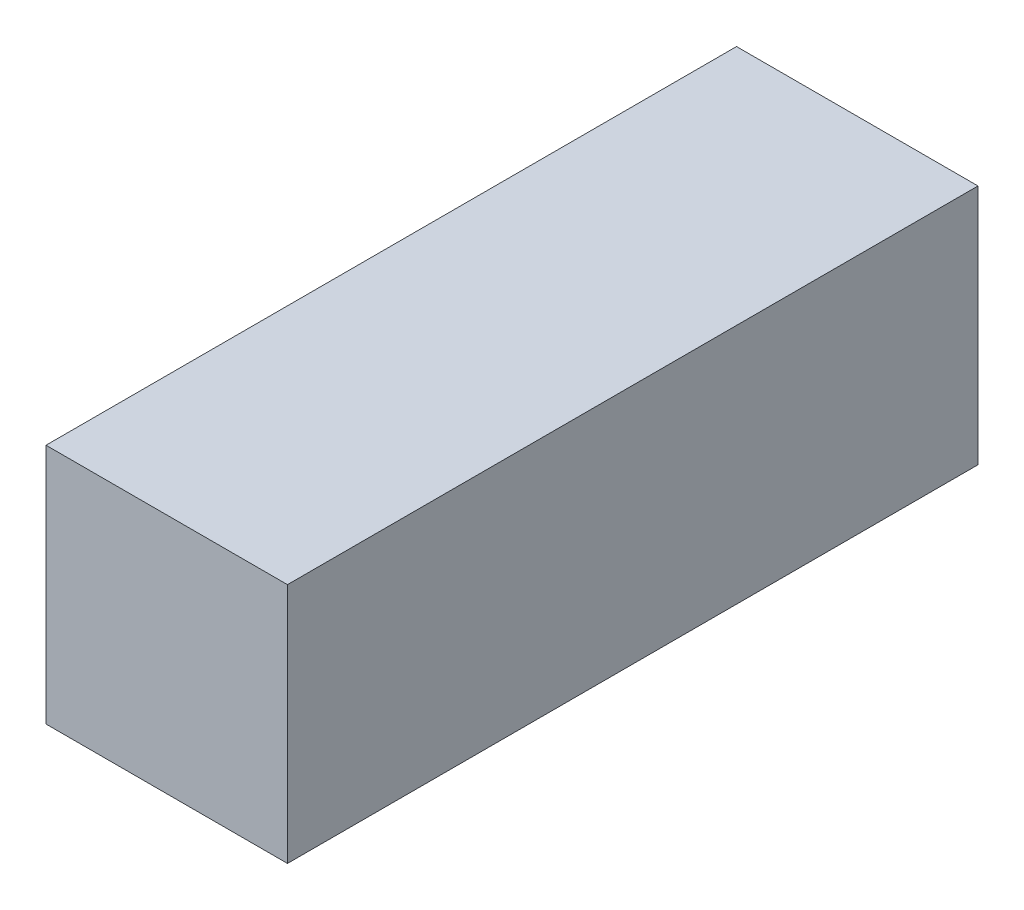
SolidWorks part; units mm, degrees
material "A-Glass Fiber"
ref_plane "Front Plane" through (0, 0, 0) normal (0, 0, 1) x (1, 0, 0)
ref_plane "Top Plane" through (0, 0, 0) normal (0, 1, 0) x (1, 0, 0)
ref_plane "Right Plane" through (0, 0, 0) normal (1, 0, 0) x (0, 0, -1)
sketch "Sketch1" plane through (0, 0, 0) normal (1, 0, 0) x (0, 0, -1)
  line L0 (-28.575, 0) -> (28.575, 0) construction
  line L1 (-28.575, 9.652) -> (28.575, 9.652)
  line L2 (-28.575, 9.652) -> (-28.575, -9.398)
  line L3 (-28.575, -9.398) -> (28.575, -9.398)
  line L4 (28.575, 9.652) -> (28.575, -9.398)
  dimension "D1" = 9.652
  dimension "D2" = 19.05
  dimension "D3" = 57.15
extrude "Boss-Extrude1" add sketch "Sketch1" along normal mid plane 19.05
sketch "Sketch2" plane through (0, 0, 0) normal (1, 0, 0) x (0, 0, -1)
  line L1 (-28.575, 9.652) -> (-28.575, -9.398) construction
  line L2 (-17.7349, -4.4901) -> (-12.827, -9.398)
  line L3 (-28.575, -9.398) -> (28.575, -9.398) construction
  line L4 (28.575, -9.398) -> (28.575, 9.652) construction
  line L5 (17.7349, -4.4901) -> (12.827, -9.398)
  line L6 (-19.795, 5.8666) -> (-18.227, 9.652)
  line L7 (12.827, -9.398) -> (-12.827, -9.398)
  line L8 (28.575, 9.652) -> (-28.575, 9.652) construction
  line L9 (-18.227, 9.652) -> (22.225, 9.652)
  line L10 (22.225, 9.652) -> (22.225, 6.35)
  line L11 (28.575, 9.652) -> (-28.575, 9.652) construction
  arc A0 (-19.795, 5.8666) -> (-17.7349, -4.4901) centre (-22.225, 0) ccw
  arc A1 (22.225, 6.35) -> (17.7349, -4.4901) centre (22.225, 0) cw
  dimension "D1" = 6.35
  dimension "D3" = 6.35
  dimension "D2" = 45
  dimension "D4" = 45
  dimension "D5" = 22.5
extrude "Cut-Extrude3" cut sketch "Sketch2" against normal through all both and the other way through all flip side to cut
sketch "Sketch7" plane through (0, 0, 0) normal (1, 0, 0) x (0, 0, -1)
  circle A0 centre (22.225, 0) radius 6.604
  arc A1 (17.7349, -4.4901) -> (22.225, 6.35) centre (22.225, 0) ccw construction
  dimension "D1" = 13.208
extrude "Cut-Extrude6" cut sketch "Sketch7" against normal mid plane 12.954
sketch "Sketch11" plane through (0, 0, 0) normal (1, 0, 0) x (0, 0, -1)
  circle A0 centre (-22.225, 0) radius 6.604
  arc A1 (-19.795, 5.8666) -> (-17.7349, -4.4901) centre (-22.225, 0) ccw construction
  dimension "D1" = 13.208
extrude "Cut-Extrude10" cut sketch "Sketch11" against normal mid plane 3.3528
sketch "Sketch8" plane through (9.525, 0, 0) normal (1, 0, 0) x (0, 0, -1)
  circle A0 centre (-22.225, 0) radius 6.604
  arc A1 (-19.795, 5.8666) -> (-17.7349, -4.4901) centre (-22.225, 0) ccw construction
  dimension "D1" = 13.208
extrude "Cut-Extrude7" cut sketch "Sketch8" against normal blind 3.556
sketch "Sketch9" plane through (-9.525, 0, 0) normal (-1, 0, 0) x (0, 0, 1)
  circle A0 centre (22.225, 0) radius 6.604
  arc A1 (17.7349, -4.4901) -> (19.795, 5.8666) centre (22.225, 0) ccw construction
  dimension "D1" = 13.208
extrude "Cut-Extrude8" cut sketch "Sketch9" against normal blind 3.556
sketch "Sketch10" plane through (0, 0, 0) normal (1, 0, 0) x (0, 0, -1)
  circle A0 centre (-22.225, 0) radius 1.5875
  circle A1 centre (22.225, 0) radius 3.175
  arc A2 (-19.795, 5.8666) -> (-17.7349, -4.4901) centre (-22.225, 0) ccw construction
  arc A3 (17.7349, -4.4901) -> (22.225, 6.35) centre (22.225, 0) ccw construction
  dimension "D1" = 3.175
  dimension "D2" = 6.35
extrude "Cut-Extrude9" cut sketch "Sketch10" against normal through all both and the other way through all
sketch "Sketch12" plane through (0, 0, 0) normal (0, 0, 1) x (1, 0, 0)
  line L0 (-9.525, 9.652) -> (9.525, 9.652) construction
  line L1 (-1.6764, 9.652) -> (1.6764, 9.652)
  line L2 (-1.6764, 9.652) -> (-1.6764, 3.175)
  line L3 (-1.6764, 3.175) -> (1.6764, 3.175)
  line L4 (1.6764, 9.652) -> (1.6764, 3.175)
  line L5 (0, -9.398) -> (0, 9.652) construction
  line L6 (-9.525, -9.398) -> (9.525, -9.398) construction
  line L7 (-1.6764, -4.6697) -> (-1.6764, 6.1013) construction
  dimension "D1" = 3.175
extrude "Cut-Extrude11" cut sketch "Sketch12" against normal through all both and the other way through all
sketch "Sketch13" plane through (0, 0, 0) normal (1, 0, 0) x (0, 0, -1)
  line L1 (-12.573, 6.4389) -> (12.4118, 6.4389)
  line L2 (-12.573, 6.4389) -> (-12.573, 3.0861)
  line L3 (-12.573, 3.0861) -> (12.4118, 3.0861)
  line L4 (12.4118, 6.4389) -> (12.4118, 3.0861)
  line L5 (-12.573, 4.7625) -> (12.4118, 4.7625) construction
  circle A0 centre (-22.225, 0) radius 1.5875 construction
  circle A2 centre (-14.0128, 4.7625) radius 0.7937
  circle A3 centre (22.225, 0) radius 3.175 construction
  dimension "D5" = 1.5875
  dimension "D6" = 7.112
  dimension "D4" = 7.112
  dimension "D1" = 3.3528
  dimension "D2" = 4.7625
  dimension "D3" = 9.652
extrude "Cut-Extrude12" cut sketch "Sketch13" against normal through all both and the other way through all
sketch "Sketch14" plane through (0, 0, 0) normal (1, 0, 0) x (0, 0, -1)
  line L0 (-15.875, -6.35) -> (-12.827, -9.398)
  line L1 (-17.5553, -4.6697) -> (-12.827, -9.398) construction
  line L2 (-12.827, -9.398) -> (12.827, -9.398)
  line L3 (12.827, -9.398) -> (15.875, -6.35)
  line L4 (15.875, -6.35) -> (-15.875, -6.35)
  line L7 (12.827, -9.398) -> (17.7349, -4.4901) construction
  line L8 (-14.351, -7.874) -> (14.351, -7.874) construction
  circle A0 centre (-22.225, 0) radius 1.5875 construction
  dimension "D1" = 6.35
extrude "Cut-Extrude13" cut sketch "Sketch14" against normal mid plane 3.175
sketch "Sketch16" plane through (0, 0, 0) normal (1, 0, 0) x (0, 0, -1)
  circle A0 centre (-12.827, -7.9375) radius 0.7937
  circle A1 centre (12.827, -7.9375) radius 0.7937
  arc A3 (-19.795, 5.8666) -> (-17.7349, -4.4901) centre (-22.225, 0) ccw construction
  dimension "D1" = 1.5875
  dimension "D2" = 1.5875
  dimension "D3" = 0.7937
extrude "Cut-Extrude14" cut sketch "Sketch16" against normal through all both and the other way through all
fillet "Fillet1" radius 3.175 4 edges at (-9.525, -9.398, 0) (9.525, -9.398, 0) (9.525, 9.652, -1.999) (-9.525, 9.652, -1.999)
sketch "Sketch18" plane through (0, 0, 0) normal (0, 0, 1) x (1, 0, 0)
  line L0 (1.6764, 3.175) -> (1.6764, -4.6697) construction
  line L1 (-1.6764, 3.175) -> (1.6764, 3.175)
  line L2 (-1.6764, 3.175) -> (-1.6764, 0)
  line L3 (-1.6764, 0) -> (1.6764, 0)
  line L4 (1.6764, 3.175) -> (1.6764, 0)
  dimension "D1" = 3.175
extrude "Cut-Extrude15" cut sketch "Sketch18" against normal through all both and the other way through all
sketch "Sketch19" plane through (0, 0, 0) normal (1, 0, 0) x (0, 0, -1)
  circle A0 centre (-22.225, 0) radius 6.604
  arc A2 (-17.5553, -4.6697) -> (-19.6978, 6.1013) centre (-22.225, 0) ccw construction
extrude "Cut-Extrude16" cut sketch "Sketch19" against normal mid plane 5.334
sketch "Sketch20" plane through (-9.525, 0, 0) normal (-1, 0, 0) x (0, 0, 1)
  line L0 (-22.225, 9.652) -> (18.227, 9.652) construction
  line L2 (-44.062, 9.652) -> (-44.062, -15.748) construction
  line L3 (-44.062, -15.748) -> (28.575, -15.748)
  line L4 (28.575, 9.652) -> (28.575, -15.748)
  line L5 (-7.7435, -15.748) -> (-7.7435, -0.6069) construction
  line L6 (-44.062, -0.6069) -> (28.575, -0.6069) construction
  line L7 (-44.062, 9.652) -> (28.575, 9.652)
  line L8 (-44.062, 9.652) -> (-44.062, -15.748)
  point P0 (-7.7435, -0.6069)
  dimension "D1" = 25.4
extrude "Boss-Extrude2" add sketch "Sketch20" against normal blind 25.4 separate body
